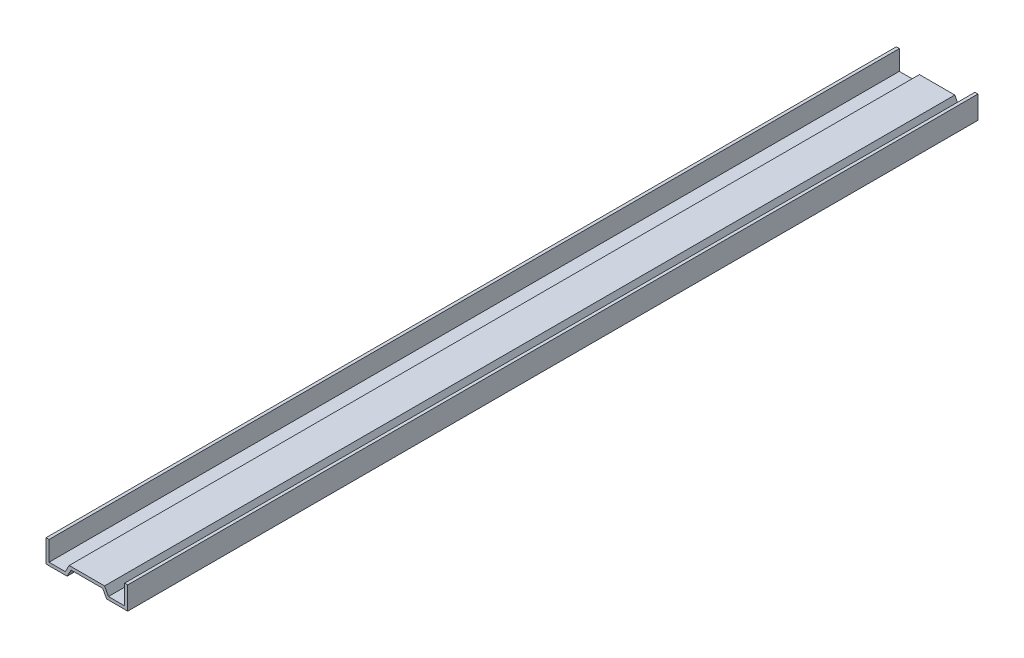
SolidWorks part; units mm, degrees
ref_plane "Front Plane" through (0, 0, 0) normal (0, 0, 1) x (1, 0, 0)
ref_plane "Top Plane" through (0, 0, 0) normal (0, 1, 0) x (1, 0, 0)
ref_plane "Right Plane" through (0, 0, 0) normal (1, 0, 0) x (0, 0, -1)
ref_plane "Plane1" through (0, 0, 362) normal (0, 0, 1) x (1, 0, 0)
sketch "Sketch1" plane through (0, 0, 362) normal (0, 0, 1) x (1, 0, 0)
  line L0 (-9.1805, -3.0955) -> (-16.1, -3.0955)
  line L1 (-16.1, -3.0955) -> (-16.1, 5.3045)
  line L2 (-16.1, 5.3045) -> (-17.4, 5.3045)
  line L3 (-17.4, 5.3045) -> (-17.4, -4.3955)
  line L4 (-17.4, -4.3955) -> (-8.4, -4.3955)
  line L5 (-8.4, -4.3955) -> (-6.7499, -1.3)
  line L6 (-6.7499, -1.3) -> (6.7501, -1.3)
  line L7 (6.7501, -1.3) -> (8.4, -4.3955)
  line L8 (8.4, -4.3955) -> (17.4, -4.3955)
  line L9 (17.4, -4.3955) -> (17.4, 5.3045)
  line L10 (17.4, 5.3045) -> (16.1, 5.3045)
  line L11 (16.1, 5.3045) -> (16.1, -3.0955)
  line L12 (16.1, -3.0955) -> (9.1802, -3.0955)
  line L13 (9.1802, -3.0955) -> (7.5303, 0)
  line L14 (7.5303, 0) -> (-7.5303, 0)
  line L15 (-7.5303, 0) -> (-9.1805, -3.0955)
extrude "Boss-Extrude1" add sketch "Sketch1" against normal blind 362
